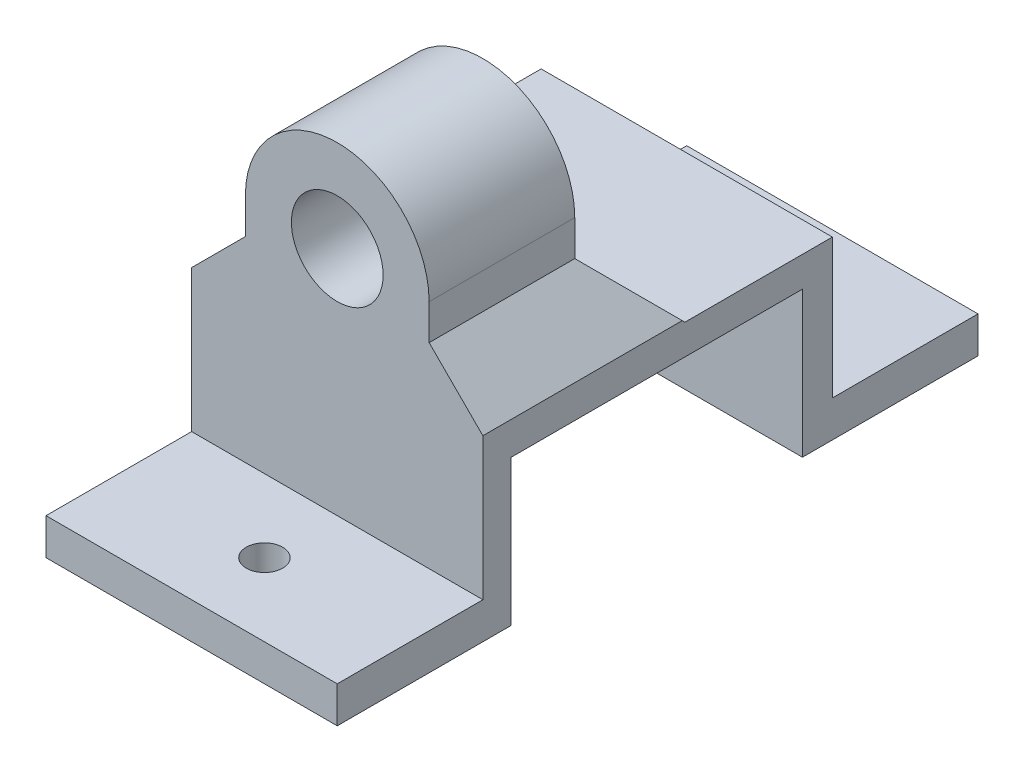
SolidWorks part; units mm, degrees
ref_plane "Front Plane" through (0, 0, 0) normal (0, 0, 1) x (1, 0, 0)
ref_plane "Top Plane" through (0, 0, 0) normal (0, 1, 0) x (1, 0, 0)
ref_plane "Right Plane" through (0, 0, 0) normal (1, 0, 0) x (0, 0, -1)
sketch "Sketch1" plane through (0, 0, 0) normal (1, 0, 0) x (0, 0, -1)
  line L0 (12.7, 0.101) -> (20.2722, 0.101) construction
  line L1 (12.7, 12.801) -> (-12.7, 12.801)
  line L2 (12.7, 12.801) -> (12.7, 0.101)
  line L4 (-12.7, 12.801) -> (-12.7, 0.101)
  line L5 (12.7, 12.801) -> (0, 0) construction
  line L6 (0, 0) -> (-12.7, 12.801) construction
  line L7 (15.3077, 15.4294) -> (-15.1723, 15.4294)
  line L8 (15.3077, 15.4294) -> (15.3077, 3.276)
  line L10 (-15.1723, 15.4294) -> (-15.1723, 3.276)
  line L11 (15.3077, 15.4294) -> (0, 0) construction
  line L12 (12.7, 0.101) -> (28.0077, 0.101)
  line L13 (-27.8723, 0.101) -> (-12.7, 0.101)
  line L14 (-27.8723, 3.276) -> (-15.1723, 3.276)
  line L15 (-27.8723, 3.276) -> (-27.8723, 0.101)
  line L17 (28.0077, 3.276) -> (28.0077, 0.101)
  line L18 (-27.8723, 3.276) -> (0, 0) construction
  line L19 (0, 0) -> (28.0077, 3.276) construction
  line L20 (15.3077, 3.276) -> (28.0077, 3.276)
  line L25 (0, 0) -> (-15.1723, 15.4294) construction
  point P0 (0, 0)
  point P1 (12.7328, 0)
  point P3 (-12.7677, 0)
  point P6 (6.35, 6.4005)
  dimension "D1" = 25.4
  dimension "D2" = 2.4723
  dimension "D3" = 3.175
  dimension "D4" = 12.7
  dimension "D5" = 15.1723
  dimension "D6" = 2.6284
  dimension "D7" = 2.6077
  dimension "D8" = 12.7
extrude "Boss-Extrude1" add sketch "Sketch1" along normal blind 25.4
sketch "Sketch2" plane through (0, 0, 15.1723) normal (0, 0, 1) x (1, 0, 0)
  line L0 (12.7, 15.4294) -> (12.7, 23.4423) construction
  line L1 (25.4, 15.4294) -> (0, 15.4294) construction
  line L4 (4.6871, 23.4423) -> (4.6871, 15.4294)
  line L5 (4.6871, 15.4294) -> (20.7129, 15.4294)
  line L6 (20.7129, 23.4423) -> (20.7129, 15.4294)
  line L7 (7.034, 29.1082) -> (20.7129, 15.4294) construction
  line L8 (4.6871, 15.4294) -> (18.366, 29.1082) construction
  circle A0 centre (12.7, 23.4423) radius 4
  arc A1 (20.7129, 23.4423) -> (4.6871, 23.4423) centre (12.7, 23.4423) ccw
  dimension "D1" = 8
extrude "Boss-Extrude2" add sketch "Sketch2" against normal blind 12.7
chamfer "Chamfer1" distance 4.92 angle 45 2 edges at (4.6871, 15.4294, 8.8223) (20.7129, 15.4294, 8.8223)
chamfer "Chamfer2" distance 4.92 angle 45 1 edges at (12.7, 15.4294, 2.4723)
sketch "Sketch3" plane through (0, 3.276, 0) normal (0, 1, 0) x (1, 0, 0)
  line L0 (12.7, 28.0077) -> (12.7, -27.8723) construction
  line L1 (25.4, 28.0077) -> (0, 28.0077) construction
  line L2 (25.4, -27.8723) -> (0, -27.8723) construction
  line L3 (25.4, -21.5223) -> (0, -21.5223) construction
  line L4 (25.4, -15.1723) -> (25.4, -27.8723) construction
  line L5 (0, -15.1723) -> (0, -27.8723) construction
  line L6 (25.4, 21.6577) -> (0, 21.6577) construction
  line L7 (25.4, 28.0077) -> (25.4, 15.3077) construction
  line L8 (0, 28.0077) -> (0, 15.3077) construction
  circle A0 centre (12.7, 21.6577) radius 1.5875
  circle A1 centre (12.7, -21.5223) radius 1.5875
  dimension "D1" = 3.175
extrude "Cut-Extrude1" cut sketch "Sketch3" against normal blind 12.7
